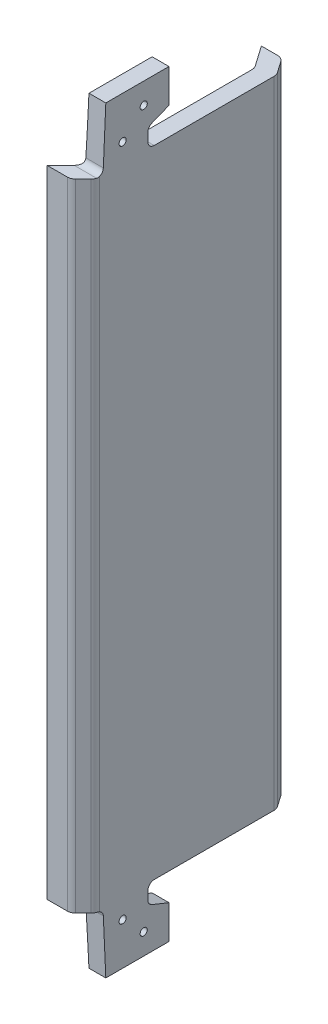
SolidWorks part; units mm, degrees
ref_plane "Front Plane" through (0, 0, 0) normal (0, 0, 1) x (1, 0, 0)
ref_plane "Top Plane" through (0, 0, 0) normal (0, 1, 0) x (1, 0, 0)
ref_plane "Right Plane" through (0, 0, 0) normal (1, 0, 0) x (0, 0, -1)
sketch "Sketch2" plane through (0, 0, 0) normal (0, 1, 0) x (1, 0, 0)
  line L0 (0, 0) -> (50000, 0) construction
  line L1 (0, 0) -> (0, 50000) construction
  line L2 (0, 0) -> (-3.81, -3.81)
  line L3 (-3.81, -3.81) -> (-10.9942, -3.81)
  line L4 (-10.9942, -3.81) -> (-5.08, 2.1042)
  line L5 (-5.08, 2.1042) -> (-5.08, 52.9042)
  line L6 (-5.08, 52.9042) -> (-9.8315, 59.69)
  line L7 (-9.8315, 59.69) -> (-3.6299, 59.69)
  line L8 (-3.6299, 59.69) -> (0, 54.5059)
  line L9 (0, 54.5059) -> (0, 0)
  dimension "D1" = 5.08
  dimension "D2" = 45
  dimension "D3" = 3.81
  dimension "D4" = 50.8
  dimension "D5" = 5.08
  dimension "D6" = 35
  dimension "D7" = 5.08
  dimension "D8" = 63.5
extrude "Boss-Extrude1" add sketch "Sketch2" along normal mid plane 191.77
sketch "Sketch3" plane through (-5.08, 0, 0) normal (-1, 0, 0) x (0, 0, 1)
  line L0 (-78.3042, 0) -> (49921.6958, 0) construction
  line L1 (-59.69, 95.885) -> (-59.69, -95.885) construction
  line L2 (-27.5042, 203.2) -> (-27.5042, -49796.8) construction
  line L3 (-52.9042, 95.885) -> (-2.1042, 95.885) construction
  line L8 (-40.64, 107.95) -> (-46.99, 107.95) construction
  line L9 (-39.37, 95.885) -> (-39.37, 101.6) construction
  line L10 (-39.37, 101.6) -> (-33.02, 104.14) construction
  line L11 (-33.02, 104.14) -> (-33.02, 114.3) construction
  line L12 (-33.02, 114.3) -> (-52.07, 114.3) construction
  line L13 (-52.07, 114.3) -> (-52.9042, 95.885) construction
  line L15 (-39.37, 95.885) -> (-52.9042, 95.885) construction
  line L16 (-40.64, -107.95) -> (-46.99, -107.95) construction
  line L17 (-39.37, -95.885) -> (-52.9042, -95.885) construction
  line L18 (-52.07, -114.3) -> (-52.9042, -95.885) construction
  line L19 (-33.02, -114.3) -> (-52.07, -114.3) construction
  line L20 (-33.02, -104.14) -> (-33.02, -114.3) construction
  line L21 (-39.37, -101.6) -> (-33.02, -104.14) construction
  line L22 (-39.37, -95.885) -> (-39.37, -101.6) construction
  line L23 (-14.3684, -107.95) -> (-8.0184, -107.95) construction
  line L24 (-14.3684, 107.95) -> (-8.0184, 107.95) construction
  line L25 (-15.6384, -95.885) -> (-15.6384, -101.6)
  line L26 (-15.6384, -101.6) -> (-21.9884, -104.14)
  line L27 (-21.9884, -104.14) -> (-21.9884, -114.3)
  line L28 (-21.9884, -114.3) -> (-2.9384, -114.3)
  line L29 (-2.9384, -114.3) -> (-2.1042, -95.885)
  line L30 (-15.6384, -95.885) -> (-2.1042, -95.885)
  line L31 (-15.6384, 95.885) -> (-2.1042, 95.885)
  line L32 (-2.9384, 114.3) -> (-2.1042, 95.885)
  line L33 (-21.9884, 114.3) -> (-2.9384, 114.3)
  line L34 (-21.9884, 104.14) -> (-21.9884, 114.3)
  line L35 (-15.6384, 101.6) -> (-21.9884, 104.14)
  line L36 (-15.6384, 95.885) -> (-15.6384, 101.6)
  circle A0 centre (-46.99, 107.95) radius 3.175 construction
  circle A1 centre (-40.64, 107.95) radius 1.0795 construction
  circle A2 centre (-46.99, 101.6) radius 1.0795 construction
  circle A3 centre (-46.99, -101.6) radius 1.0795 construction
  circle A4 centre (-40.64, -107.95) radius 1.0795 construction
  circle A5 centre (-46.99, -107.95) radius 3.175 construction
  circle A6 centre (-8.0184, -107.95) radius 3.175 construction
  circle A7 centre (-14.3684, -107.95) radius 1.0795 construction
  circle A8 centre (-8.0184, -101.6) radius 1.0795 construction
  circle A9 centre (-8.0184, 101.6) radius 1.0795 construction
  circle A10 centre (-14.3684, 107.95) radius 1.0795 construction
  circle A11 centre (-8.0184, 107.95) radius 3.175 construction
  point P4 (-59.69, 0)
  point P9 (-27.5042, 95.885)
  dimension "D3" = 2.159
  dimension "D4" = 2.159
  dimension "D7" = 6.35
  dimension "D2" = 12.7
  dimension "D5" = 6.35
  dimension "D6" = 6.35
  dimension "D8" = 12.7
  dimension "D9" = 20.32
  dimension "D10" = 203.2
  dimension "D11" = 208.28
  dimension "D13" = 26.67
  dimension "D14" = 7.62
  dimension "D15" = 215.9
  dimension "D12" = 114.3
extrude "Boss-Extrude2" add sketch "Sketch3" against normal up to surface (5.08 mm away) up to face at (0, 0, -27.253)
sketch "Sketch4" plane through (-5.08, 0, 0) normal (-1, 0, 0) x (0, 0, 1)
  circle A0 centre (-40.64, 107.95) radius 1.0795
  circle A1 centre (-46.99, 101.6) radius 1.0795
  circle A2 centre (-40.64, 107.95) radius 3.429
  circle A3 centre (-46.99, 101.6) radius 3.429
  circle A4 centre (-40.64, 107.95) radius 1.0795 construction
  circle A5 centre (-46.99, 101.6) radius 1.0795 construction
  dimension "D1" = 6.858
  dimension "D2" = 6.858
sketch "Sketch5" plane through (-5.08, 0, 0) normal (-1, 0, 0) x (0, 0, 1)
  circle A0 centre (-8.0184, -101.6) radius 1.0795 construction
  circle A1 centre (-14.3684, -107.95) radius 1.0795 construction
  circle A2 centre (-8.0184, 101.6) radius 1.0795 construction
  circle A3 centre (-14.3684, 107.95) radius 1.0795 construction
  circle A8 centre (-40.64, -107.95) radius 1.0795 construction
  circle A9 centre (-46.99, -101.6) radius 1.0795 construction
  circle A11 centre (-46.99, 101.6) radius 1.0795 construction
  circle A12 centre (-40.64, 107.95) radius 1.0795 construction
  circle A13 centre (-40.64, -107.95) radius 1.0795
  circle A14 centre (-46.99, -101.6) radius 1.0795
  circle A15 centre (-46.99, 101.6) radius 1.0795
  circle A16 centre (-40.64, 107.95) radius 1.0795
  circle A17 centre (-8.0184, -101.6) radius 1.0795
  circle A18 centre (-14.3684, -107.95) radius 1.0795
  circle A19 centre (-8.0184, 101.6) radius 1.0795
  circle A20 centre (-14.3684, 107.95) radius 1.0795
extrude "Cut-Extrude1" cut sketch "Sketch5" against normal through all
fillet "Fillet2" radius 1.905 6 edges at (-2.54, -101.6, -15.6384) (-2.54, -95.885, -15.6384) (-2.54, 101.6, -15.6384) (-2.54, 95.885, -15.6384) (-2.54, 95.885, -2.1042) (-2.54, -95.885, -2.1042)
fillet "Fillet3" radius 2.54 6 edges at (-3.6299, 0, -59.69) (-3.81, 0, 3.81) (0, 0, -54.5059) (0, 0, 0) (-5.08, 0, -52.9042) (-5.08, 0, -2.1042)
equation "\"D4@Sketch3\"=\"D3@Sketch3\""
equation "\"D8@Sketch3\"=\"D2@Sketch3\""
equation "\"D2@Sketch4\"=\"D1@Sketch4\""
